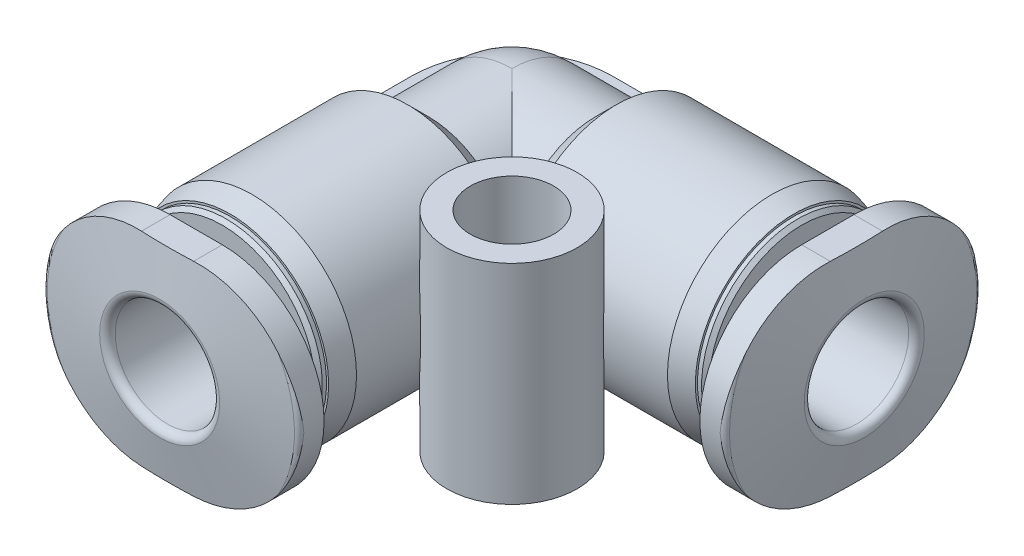
SolidWorks part; units mm, degrees
ref_plane "Ebene vorne" through (0, 0, 0) normal (0, 0, 1) x (1, 0, 0)
ref_plane "Ebene oben" through (0, 0, 0) normal (0, 1, 0) x (1, 0, 0)
ref_plane "Ebene rechts" through (0, 0, 0) normal (1, 0, 0) x (0, 0, -1)
sketch "Skizze1" plane through (0, 0, 0) normal (0, 0, 1) x (1, 0, 0)
  line L0 (0, 3.2) -> (3.2, 3.2)
  line L1 (3.2, 3.2) -> (4, 4)
  line L2 (4, 4) -> (9.9571, 4)
  line L3 (9.9571, 4) -> (10.8, 3.7742)
  line L4 (10.8, 3.7742) -> (10.8, 3.6938)
  line L5 (10.8, 3.6938) -> (10.9586, 3.6938)
  line L6 (10.9586, 3.6938) -> (11.1, 3.5524)
  line L7 (11.1, 3.5524) -> (11.1, 2.7)
  line L8 (11.1, 2.7) -> (11.73, 2.7)
  line L9 (12.1, 3.07) -> (12.1, 4.9)
  line L10 (12.1, 4.9) -> (12.8737, 4.9)
  line L11 (13.0707, 4.7347) -> (13.5, 2.3)
  line L12 (13.5, 2.3) -> (13.5, 0)
  line L13 (13.5, 0) -> (-3.2, 0)
  line L14 (13.5, 0) -> (-3.2, 0) construction
  arc A0 (-3.2, 0) -> (0, 3.2) centre (0, 0) cw
  arc A1 (11.73, 2.7) -> (12.1, 3.07) centre (11.73, 3.07) ccw
  arc A2 (12.8737, 4.9) -> (13.0707, 4.7347) centre (12.8737, 4.7) cw
revolve "Rotation1" add sketch "Skizze1" angle 360 about L14
ref_plane "Ebene1" through (13.5, 0, 0) normal (1, 0, 0) x (0, 0, -1)
sketch "Skizze2" plane through (13.5, 0, 0) normal (1, 0, 0) x (0, 0, -1)
  line L0 (-5.88, -3.3948) -> (0, -6.7896)
  line L1 (0, -6.7896) -> (5.88, -3.3948)
  line L2 (5.88, -3.3948) -> (5.88, 3.3948)
  line L3 (5.88, 3.3948) -> (0, 6.7896)
  line L4 (0, 6.7896) -> (-5.88, 3.3948)
  line L5 (-5.88, 3.3948) -> (-5.88, -3.3948)
  line L6 (-1, -3.9) -> (1, -3.9)
  line L7 (1, 3.9) -> (-1, 3.9)
  arc A0 (-4.9, 0) -> (-1, -3.9) centre (-1, 0) ccw
  arc A1 (1, -3.9) -> (4.9, 0) centre (1, 0) ccw
  arc A2 (4.9, 0) -> (1, 3.9) centre (1, 0) ccw
  arc A3 (-1, 3.9) -> (-4.9, 0) centre (-1, 0) ccw
extrude "Schnitt-Linear austragen1" cut sketch "Skizze2" against normal blind 1.4
sketch "Skizze3" plane through (0, 0, 0) normal (1, 0, 0) x (0, 0, -1)
  line L0 (-3.873, -1) -> (3.873, -1)
  line L1 (3.873, 1) -> (-3.873, 1)
  arc A0 (-3.873, 1) -> (-3.873, -1) centre (0, 0) ccw
  arc A1 (3.873, -1) -> (3.873, 1) centre (0, 0) ccw
extrude "Aufsatz-Linear austragen1" add sketch "Skizze3" along normal blind 4
sketch "Skizze4" plane through (0, 0, 0) normal (0, 1, 0) x (1, 0, 0)
  line L0 (0, 1.5) -> (2, 1.5)
  line L1 (2, 1.5) -> (2, 1.8)
  line L2 (2.2, 2) -> (13.2, 2)
  line L3 (13.5, 2.3) -> (13.5, 0)
  line L4 (13.5, 0) -> (-1.5, 0)
  line L5 (13.5, 0) -> (-1.5, 0) construction
  arc A0 (-1.5, 0) -> (0, 1.5) centre (0, 0) cw
  arc A1 (2, 1.8) -> (2.2, 2) centre (2.2, 1.8) cw
  arc A2 (13.2, 2) -> (13.5, 2.3) centre (13.2, 2.3) ccw
sketch "Skizze5" plane through (0, 0, 0) normal (0, 0, 1) x (1, 0, 0)
  line L0 (-3.873, -1) -> (0, -1)
  line L1 (0, -1) -> (0, 1)
  line L2 (0, 1) -> (-3.873, 1)
  arc A0 (-3.873, 1) -> (-3.873, -1) centre (0, 0) ccw
extrude "Aufsatz-Linear austragen2" add sketch "Skizze5" along normal blind 4
sketch "Skizze6" plane through (0, 0, 0) normal (1, 0, 0) x (0, 0, -1)
  line L0 (0, 0) -> (0, -3.2)
  line L1 (0, -3.2) -> (-3.2, -3.2)
  line L2 (-3.2, -3.2) -> (-4, -4)
  line L3 (-4, -4) -> (-9.9571, -4)
  line L4 (-9.9571, -4) -> (-10.8, -3.7742)
  line L5 (-10.8, -3.7742) -> (-10.8, -3.6938)
  line L6 (-10.8, -3.6938) -> (-10.9586, -3.6938)
  line L7 (-10.9586, -3.6938) -> (-11.1, -3.5524)
  line L8 (-11.1, -3.5524) -> (-11.1, -2.7)
  line L9 (-11.1, -2.7) -> (-11.73, -2.7)
  line L10 (-12.1, -3.07) -> (-12.1, -4.9)
  line L11 (-12.1, -4.9) -> (-12.8737, -4.9)
  line L12 (-13.0707, -4.7347) -> (-13.5, -2.3)
  line L13 (-13.5, -2.3) -> (-13.5, 0)
  line L14 (-13.5, 0) -> (0, 0)
  line L15 (-13.5, 0) -> (0, 0) construction
  arc A0 (-11.73, -2.7) -> (-12.1, -3.07) centre (-11.73, -3.07) ccw
  arc A1 (-12.8737, -4.9) -> (-13.0707, -4.7347) centre (-12.8737, -4.7) cw
revolve "Rotation2" add sketch "Skizze6" angle 360 about L15 reverse direction yes
ref_plane "Ebene2" through (0, 0, 13.5) normal (0, 0, 1) x (1, 0, 0)
sketch "Skizze7" plane through (0, 0, 13.5) normal (0, 0, 1) x (1, 0, 0)
  line L0 (-5.88, -3.3948) -> (0, -6.7896)
  line L1 (0, -6.7896) -> (5.88, -3.3948)
  line L2 (5.88, -3.3948) -> (5.88, 3.3948)
  line L3 (5.88, 3.3948) -> (0, 6.7896)
  line L4 (0, 6.7896) -> (-5.88, 3.3948)
  line L5 (-5.88, 3.3948) -> (-5.88, -3.3948)
  line L6 (-1, -3.9) -> (1, -3.9)
  line L7 (1, 3.9) -> (-1, 3.9)
  arc A0 (-4.9, 0) -> (-1, -3.9) centre (-1, 0) ccw
  arc A1 (1, -3.9) -> (4.9, 0) centre (1, 0) ccw
  arc A2 (4.9, 0) -> (1, 3.9) centre (1, 0) ccw
  arc A3 (-1, 3.9) -> (-4.9, 0) centre (-1, 0) ccw
extrude "Schnitt-Linear austragen2" cut sketch "Skizze7" against normal blind 1.4
sketch "Skizze8" plane through (0, 0, 0) normal (1, 0, 0) x (0, 0, -1)
  line L0 (0, 0) -> (0, -1.5)
  line L1 (0, -1.5) -> (-2, -1.5)
  line L2 (-2, -1.5) -> (-2, -1.8)
  line L3 (-2.2, -2) -> (-13.2, -2)
  line L4 (-13.5, -2.3) -> (-13.5, 0)
  line L5 (-13.5, 0) -> (0, 0)
  line L6 (-13.5, 0) -> (0, 0) construction
  arc A0 (-2, -1.8) -> (-2.2, -2) centre (-2.2, -1.8) cw
  arc A1 (-13.2, -2) -> (-13.5, -2.3) centre (-13.2, -2.3) ccw
sketch "Skizze9" plane through (0, 0, 0) normal (0, 1, 0) x (1, 0, 0)
  circle A0 centre (5.5, -5.5) radius 2.5
extrude "Aufsatz-Linear austragen3" add sketch "Skizze9" against normal blind 4 and the other way blind 4
hole_wizard "Bohrung1" positions "Skizze11" profile "Skizze10" legacy
sketch "Skizze11" plane through (0, 4, 0) normal (0, 1, 0) x (1, 0, 0)
  point P0 (5.5, -5.5)
sketch "Skizze10" plane through (5.5, 4, 5.5) normal (1, 0, 0) x (0, 0, 1)
  line L0 (0, 0) -> (0, 9)
  line L1 (0, 9) -> (1.6, 9)
  line L2 (1.6, 9) -> (1.6, 0)
  line L3 (1.6, 0) -> (0, 0)
  line L4 (0, 110) -> (0, -10) construction
  dimension "Durchmesser" = 3.2
  dimension "Tiefe" = 9
sketch "Skizze12" plane through (0, 0, 0) normal (1, 0, 0) x (0, 0, -1)
  line L0 (0, 1) -> (3.873, 1)
  line L1 (3.873, -1) -> (0, -1)
  line L2 (0, -1) -> (0, 1)
  line L3 (0, -1) -> (0, 1) construction
  arc A0 (3.873, 1) -> (3.873, -1) centre (0, 0) cw
revolve "Rotation3" add sketch "Skizze12" angle 90 about L3
revolve "Schnitt-Rotation1" cut sketch "Skizze8" angle 360 about L6 reverse direction yes
revolve "Schnitt-Rotation2" cut sketch "Skizze4" angle 360 about L5 reverse direction yes
